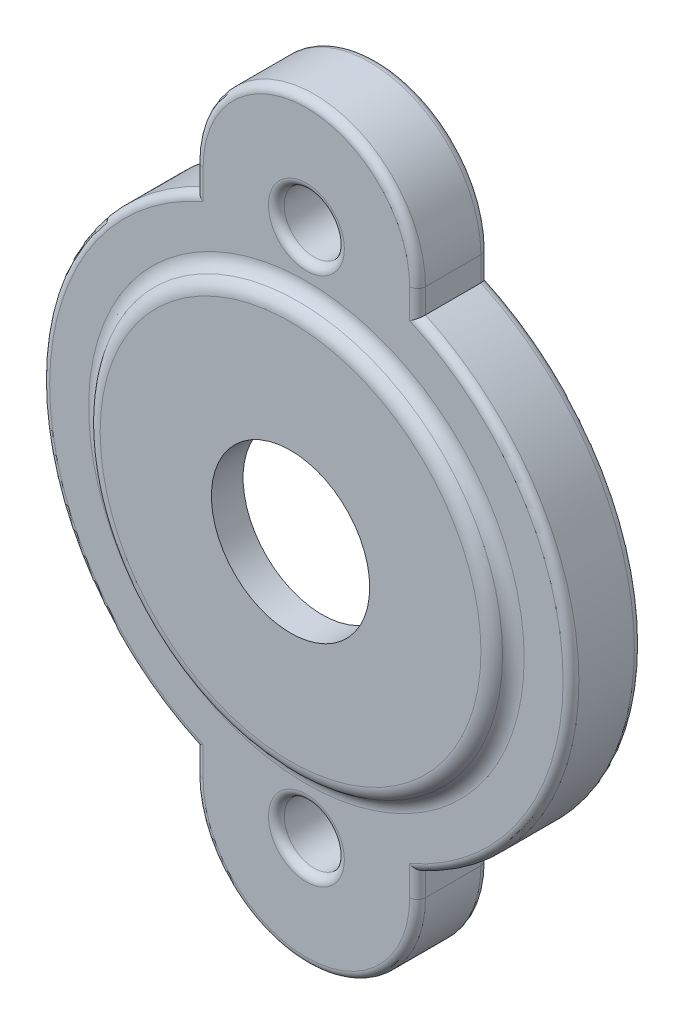
SolidWorks part; units mm, degrees
ref_plane "Front Plane" through (0, 0, 0) normal (0, 0, 1) x (1, 0, 0)
ref_plane "Top Plane" through (0, 0, 0) normal (0, 1, 0) x (1, 0, 0)
ref_plane "Right Plane" through (0, 0, 0) normal (1, 0, 0) x (0, 0, -1)
sketch "Sketch1" plane through (0, 0, 0) normal (0, 0, 1) x (1, 0, 0)
  line L0 (3.1, 17.7826) -> (3.1, 51.2174) construction
  line L1 (-3.9245, 17.7826) -> (-3.9245, 19.33)
  line L2 (10.1245, 17.7826) -> (10.1245, 19.33)
  line L3 (10.1245, 49.67) -> (10.1245, 51.2174)
  line L4 (-3.9245, 49.67) -> (-3.9245, 51.2174)
  arc A0 (10.1245, 19.33) -> (10.1245, 49.67) centre (3.1, 34.5) ccw
  circle A1 centre (3.1, 34.5) radius 10.9
  arc A2 (-10.1054, 24.2488) -> (-3.9245, 19.33) centre (3.1, 34.5) ccw
  arc A3 (-3.9245, 17.7826) -> (10.1245, 17.7826) centre (3.1, 17.7826) ccw
  arc A4 (10.1245, 51.2174) -> (-3.9245, 51.2174) centre (3.1, 51.2174) ccw
  arc A5 (-3.9245, 49.67) -> (-10, 44.8856) centre (3.1, 34.5) ccw
  circle A6 centre (3.1, 51.2174) radius 1.9
  circle A7 centre (3.1, 17.7826) radius 1.9
  arc A8 (-3.9245, 49.67) -> (-3.9245, 19.33) centre (3.1, 34.5) ccw
  arc A9 (10.1245, 19.33) -> (10.1245, 49.67) centre (3.1, 34.5) ccw
  point P5 (3.1, 34.5)
extrude "Boss-Extrude1" add sketch "Sketch1" along normal blind 4.5 contours A5 A8 A2 L1 A3 L2 A0 L3 A4 L4 A7 A1 A6 region at (-3.3437, 18.5563, 0)
sketch "Sketch2" plane through (0, 0, 4.5) normal (0, 0, 1) x (1, 0, 0)
  circle A0 centre (3.1, 34.5) radius 12.7596
  circle A1 centre (3.1, 34.5) radius 5
  dimension "D1" = 10
extrude "Boss-Extrude2" add sketch "Sketch2" along normal blind 1 and the other way blind 1
fillet "Fillet1" radius 1 1 edges at (15.8596, 34.5, 4.5)
fillet "Fillet2" radius 1 1 edges at (15.8596, 34.5, 5.5)
fillet "Fillet3" radius 0.5 21 edges at (-3.9245, 18.5563, 0) (3.1, 10.7582, 0) (10.1245, 18.5563, 0) (19.8174, 34.5, 0) (10.1245, 50.4437, 0) (3.1, 58.2418, 0) (-3.9245, 50.4437, 0) (-13.6174, 34.5, 0) (5, 17.7826, 0) (5, 51.2174, 0) (14, 34.5, 0) (-3.9245, 50.4437, 4.5) (3.1, 58.2418, 4.5) (10.1245, 50.4437, 4.5) (19.8174, 34.5, 4.5) (10.1245, 18.5563, 4.5) (3.1, 10.7582, 4.5) (-3.9245, 18.5563, 4.5) (-13.6174, 34.5, 4.5) (5, 17.7826, 4.5) (5, 51.2174, 4.5) tangent propagation no
